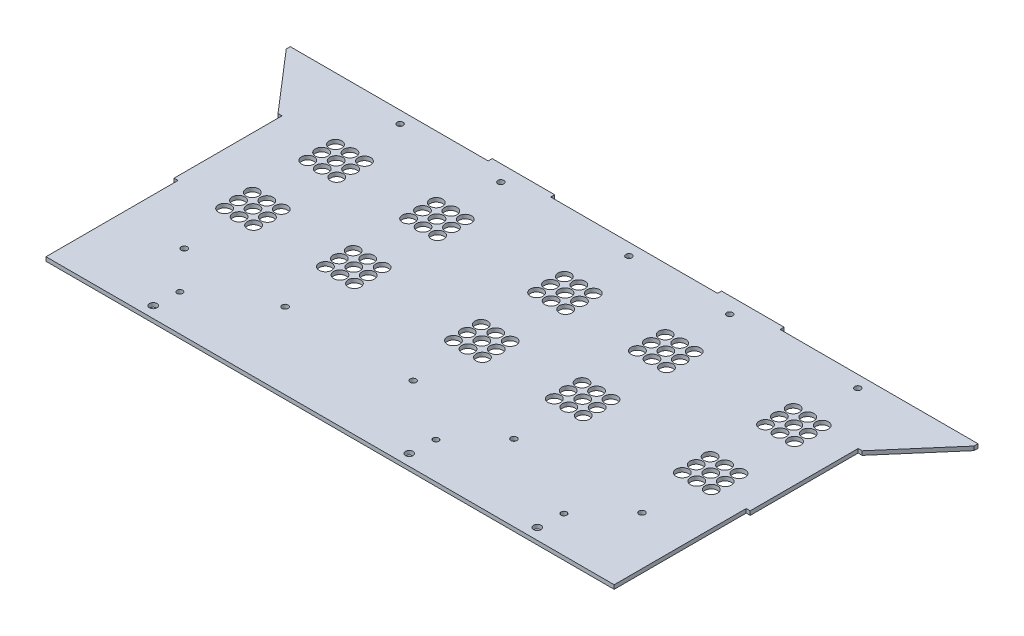
SolidWorks part; units mm, degrees
material "6061-T6 (SS)"
ref_plane "X-Y Datum" through (0, 0, 0) normal (0, 0, 1) x (1, 0, 0)
ref_plane "X-Z Datum" through (0, 0, 0) normal (0, 1, 0) x (1, 0, 0)
ref_plane "Y-Z Datum" through (0, 0, 0) normal (1, 0, 0) x (0, 0, -1)
sketch "Sketch1" plane through (0, 0, 0) normal (0, 0, 1) x (1, 0, 0)
  line L1 (-228.6114, -1.5875) -> (228.6114, -1.5875)
  line L2 (-228.6114, -1.5875) -> (-228.6114, 1.5875)
  line L3 (-228.6114, 1.5875) -> (228.6114, 1.5875)
  line L4 (228.6114, -1.5875) -> (228.6114, 1.5875)
  line L5 (-228.6114, -1.5875) -> (228.6114, 1.5875) construction
  line L6 (-228.6114, 1.5875) -> (228.6114, -1.5875) construction
  point P0 (0, 0)
  dimension "D1" = 3.175
  dimension "D2" = 457.2229
extrude "Boss-Extrude1" add sketch "Sketch1" along normal blind 241.2744
sketch "Sketch4" plane through (0, -1.5875, 0) normal (0, -1, 0) x (1, 0, 0)
  line L0 (-228.6114, 0) -> (-272.8862, 0)
  line L2 (-228.6114, 241.2744) -> (-228.6114, 0) construction
  line L3 (-228.6114, 50.8) -> (-228.6114, 0)
  line L4 (-272.8862, 0) -> (-272.8862, 3.175)
  line L6 (-228.6114, 50.8) -> (-231.7864, 50.8)
  line L7 (-231.7864, 50.8) -> (-272.8862, 3.175)
  line L31 (-228.6114, 0) -> (228.6114, 0)
  line L40 (-228.6114, 241.2744) -> (-228.6114, 0)
  line L41 (228.6114, 241.2744) -> (-228.6114, 241.2744)
  line L42 (228.6114, 0) -> (228.6114, 241.2744)
  line L51 (-228.6114, 0) -> (228.6114, 0)
  line L60 (-228.6114, 241.2744) -> (-228.6114, 0)
  line L61 (228.6114, 241.2744) -> (-228.6114, 241.2744)
  line L62 (228.6114, 0) -> (228.6114, 241.2744)
  point P2 (0, 0)
  point P11 (-271.03, 3.175)
  line M15 (-228.6114, 241.2744) -> (-228.6114, 0)
  dimension "D1" = 44.2747
  dimension "D2" = 50.8
  dimension "D3" = 3.175
  dimension "D4" = 3.175
  dimension "D5" = 0
extrude "Boss-Extrude3" add sketch "Sketch4" against normal blind 3.175 contours L6 L7 L4 L0 M15 region at (-244.2491, -1.5875, 18.0626)
mirror "Mirror1" about plane through (0, 0, 0) normal (1, 0, 0) of "Boss-Extrude3"
sketch "Sketch5" plane through (0, -1.5875, 0) normal (0, -1, 0) x (1, 0, 0)
  line L1 (-228.6114, 241.2744) -> (-225.4364, 241.2744)
  line L2 (-228.6114, 241.2744) -> (-228.6114, 136.4994)
  line L3 (-228.6114, 136.4994) -> (-225.4364, 136.4994)
  line L4 (-225.4364, 241.2744) -> (-225.4364, 136.4994)
  dimension "D1" = 3.175
  dimension "D2" = 104.775
extrude "Cut-Extrude2" cut sketch "Sketch5" against normal blind 3.175
mirror "Mirror2" about plane through (0, 0, 0) normal (1, 0, 0) of "Cut-Extrude2"
sketch "Sketch37" plane through (0, 1.5875, 0) normal (0, 1, 0) x (1, 0, 0)
  line L0 (-149.2364, -241.2744) -> (-149.2364, -232.3844) construction
  line L1 (225.4364, -241.2744) -> (-225.4364, -241.2744) construction
  line L2 (-225.4364, -136.4994) -> (-225.4364, -241.2744) construction
  circle A0 centre (-149.2364, -232.3844) radius 3
  dimension "D1" = 8.89
  dimension "D3" = 6
  dimension "D2" = 76.2
extrude "Cut-Extrude12" cut sketch "Sketch37" against normal blind 3.175
pattern_linear "LPattern31" count 4 spacing 101.6 along (1, 0, 0) skipping (1, 0) of "Cut-Extrude12"
sketch "Sketch51" plane through (0, 1.5875, 0) normal (0, 1, 0) x (1, 0, 0)
  point P0 (-176.2216, -180.775)
  point P1 (-176.2216, -9.525)
  point P3 (-96.2064, -9.525)
  point P5 (-96.2064, -180.775)
hole_wizard "M4 Clearance Hole1" positions "Sketch55" profile "Sketch53" hole size "M4" standard "ANSI Metric" end condition up to next
sketch "Sketch55" plane through (0, 1.5875, 0) normal (0, 1, 0) x (1, 0, 0)
  point P0 (-176.2216, -180.775)
  point P3 (-176.2216, -9.525)
sketch "Sketch53" plane through (-176.2216, 1.5875, 180.775) normal (1, 0, 0) x (0, 0, 1)
  line L0 (0, 0) -> (0, 3.175)
  line L1 (0, 3.175) -> (2.4, 3.175)
  line L2 (2.4, 3.175) -> (2.4, 0)
  line L5 (2.4, 0) -> (0, 0)
  line L11 (0, -6.35) -> (0, 107.95) construction
  dimension "Thru Hole Dia." = 4.8
  dimension "Thru Hole Depth" = 3.175
hole_wizard "M4 Clearance Hole2" positions "Sketch58" profile "Sketch57" hole size "M4" standard "ANSI Metric" end condition up to next
sketch "Sketch58" plane through (0, 1.5875, 0) normal (0, 1, 0) x (1, 0, 0)
  point P0 (-96.2064, -180.775)
  point P3 (-96.2064, -9.525)
sketch "Sketch57" plane through (-96.2064, 1.5875, 180.775) normal (1, 0, 0) x (0, 0, 1)
  line L0 (0, 0) -> (0, 3.175)
  line L1 (0, 3.175) -> (2.4, 3.175)
  line L2 (2.4, 3.175) -> (2.4, 0)
  line L5 (2.4, 0) -> (0, 0)
  line L11 (0, -6.35) -> (0, 107.95) construction
  dimension "Thru Hole Dia." = 4.8
  dimension "Thru Hole Depth" = 3.175
pattern_linear "LPattern32" count 3 spacing 181.614 along (1, 0, 0) of "M4 Clearance Hole1"
pattern_linear "LPattern33" count 2 spacing 181.614 along (1, 0, 0) of "M4 Clearance Hole2"
sketch "Sketch59" plane through (0, 1.5875, 0) normal (0, 1, 0) x (1, 0, 0)
  circle A0 centre (-187.7216, -115.2567) radius 5 construction
  circle A1 centre (-176.2216, -115.2567) radius 5 construction
  circle A2 centre (-164.7216, -115.2567) radius 5 construction
  circle A3 centre (-164.7216, -126.2567) radius 5 construction
  circle A4 centre (-176.2216, -126.2567) radius 5 construction
  circle A5 centre (-187.7216, -126.2567) radius 5 construction
  circle A6 centre (-187.7216, -137.2567) radius 5 construction
  circle A7 centre (-176.2216, -137.2567) radius 5 construction
  circle A8 centre (-164.7216, -137.2567) radius 5 construction
  circle A9 centre (-187.7216, -115.2567) radius 5
  circle A10 centre (-176.2216, -115.2567) radius 5
  circle A11 centre (-164.7216, -115.2567) radius 5
  circle A12 centre (-164.7216, -126.2567) radius 5
  circle A13 centre (-176.2216, -126.2567) radius 5
  circle A14 centre (-187.7216, -126.2567) radius 5
  circle A15 centre (-187.7216, -137.2567) radius 5
  circle A16 centre (-176.2216, -137.2567) radius 5
  circle A17 centre (-164.7216, -137.2567) radius 5
  circle A18 centre (-187.7216, -71.2567) radius 5 construction
  circle A19 centre (-176.2216, -71.2567) radius 5 construction
  circle A20 centre (-164.7216, -71.2567) radius 5 construction
  circle A21 centre (-176.2216, -60.2567) radius 5 construction
  circle A22 centre (-187.7216, -60.2567) radius 5 construction
  circle A23 centre (-187.7216, -49.2567) radius 5 construction
  circle A24 centre (-176.2216, -49.2567) radius 5 construction
  circle A25 centre (-164.7216, -49.2567) radius 5 construction
  circle A26 centre (-164.7216, -60.2567) radius 5 construction
  circle A27 centre (-187.7216, -71.2567) radius 5
  circle A28 centre (-176.2216, -71.2567) radius 5
  circle A29 centre (-164.7216, -71.2567) radius 5
  circle A30 centre (-176.2216, -60.2567) radius 5
  circle A31 centre (-187.7216, -60.2567) radius 5
  circle A32 centre (-187.7216, -49.2567) radius 5
  circle A33 centre (-176.2216, -49.2567) radius 5
  circle A34 centre (-164.7216, -49.2567) radius 5
  circle A35 centre (-164.7216, -60.2567) radius 5
  circle A36 centre (-107.7064, -126.2567) radius 5 construction
  circle A37 centre (-107.7064, -115.2567) radius 5 construction
  circle A38 centre (-107.7064, -137.2567) radius 5 construction
  circle A39 centre (-96.2064, -137.2567) radius 5 construction
  circle A40 centre (-96.2064, -126.2567) radius 5 construction
  circle A41 centre (-96.2064, -115.2567) radius 5 construction
  circle A42 centre (-84.7064, -115.2567) radius 5 construction
  circle A43 centre (-84.7064, -126.2567) radius 5 construction
  circle A44 centre (-84.7064, -137.2567) radius 5 construction
  circle A45 centre (-107.7064, -126.2567) radius 5
  circle A46 centre (-107.7064, -115.2567) radius 5
  circle A47 centre (-107.7064, -137.2567) radius 5
  circle A48 centre (-96.2064, -137.2567) radius 5
  circle A49 centre (-96.2064, -126.2567) radius 5
  circle A50 centre (-96.2064, -115.2567) radius 5
  circle A51 centre (-84.7064, -115.2567) radius 5
  circle A52 centre (-84.7064, -126.2567) radius 5
  circle A53 centre (-84.7064, -137.2567) radius 5
  circle A54 centre (-84.7064, -49.2567) radius 5 construction
  circle A55 centre (-96.2064, -49.2567) radius 5 construction
  circle A56 centre (-107.7064, -49.2567) radius 5 construction
  circle A57 centre (-107.7064, -60.2567) radius 5 construction
  circle A58 centre (-107.7064, -71.2567) radius 5 construction
  circle A59 centre (-96.2064, -71.2567) radius 5 construction
  circle A60 centre (-96.2064, -60.2567) radius 5 construction
  circle A61 centre (-84.7064, -60.2567) radius 5 construction
  circle A62 centre (-84.7064, -71.2567) radius 5 construction
  circle A63 centre (-84.7064, -49.2567) radius 5
  circle A64 centre (-96.2064, -49.2567) radius 5
  circle A65 centre (-107.7064, -49.2567) radius 5
  circle A66 centre (-107.7064, -60.2567) radius 5
  circle A67 centre (-107.7064, -71.2567) radius 5
  circle A68 centre (-96.2064, -71.2567) radius 5
  circle A69 centre (-96.2064, -60.2567) radius 5
  circle A70 centre (-84.7064, -60.2567) radius 5
  circle A71 centre (-84.7064, -71.2567) radius 5
extrude "Cut-Extrude13" cut sketch "Sketch59" against normal through all contours A34 | A33 | A32 | A31 | A35 | A29 | A28 | A27 | A15 | A16 | A17 | A12 | A13 | A14 | A11 | A10 | A9 | A30 region at (-187.7216, 1.5875, 115.2567) region at (-176.2216, 1.5875, 115.2567) region at (-164.7216, 1.5875, 115.2567) region at (-164.7216, 1.5875, 126.2567) region at (-176.2216, 1.5875, 126.2567) region at (-187.7216, 1.5875, 126.2567) region at (-187.7216, 1.5875, 137.2567) region at (-176.2216, 1.5875, 137.2567) region at (-164.7216, 1.5875, 137.2567) region at (-187.7216, 1.5875, 71.2567) region at (-176.2216, 1.5875, 71.2567) region at (-164.7216, 1.5875, 71.2567) region at (-187.7216, 1.5875, 60.2567) region at (-187.7216, 1.5875, 49.2567) region at (-176.2216, 1.5875, 49.2567) region at (-164.7216, 1.5875, 49.2567) region at (-164.7216, 1.5875, 60.2567)
pattern_linear "LPattern34" count 3 spacing 181.614 along (1, 0, 0) of "Cut-Extrude13"
sketch "Sketch60" plane through (0, 1.5875, 0) normal (0, 1, 0) x (1, 0, 0)
  circle A1 centre (-164.7216, -137.2567) radius 5
  circle A2 centre (-164.7216, -137.2567) radius 5
  circle A3 centre (-176.2216, -137.2567) radius 5
  circle A4 centre (-176.2216, -137.2567) radius 5
  circle A5 centre (-187.7216, -137.2567) radius 5
  circle A6 centre (-187.7216, -137.2567) radius 5
  circle A7 centre (-187.7216, -126.2567) radius 5
  circle A8 centre (-187.7216, -126.2567) radius 5
  circle A9 centre (-176.2216, -126.2567) radius 5
  circle A10 centre (-176.2216, -126.2567) radius 5
  circle A11 centre (-164.7216, -126.2567) radius 5
  circle A12 centre (-164.7216, -126.2567) radius 5
  circle A13 centre (-164.7216, -115.2567) radius 5
  circle A14 centre (-164.7216, -115.2567) radius 5
  circle A15 centre (-176.2216, -115.2567) radius 5
  circle A16 centre (-176.2216, -115.2567) radius 5
  circle A17 centre (-187.7216, -115.2567) radius 5
  circle A18 centre (-187.7216, -115.2567) radius 5
  circle A19 centre (-164.7216, -71.2567) radius 5
  circle A20 centre (-164.7216, -71.2567) radius 5
  circle A21 centre (-176.2216, -71.2567) radius 5
  circle A22 centre (-176.2216, -71.2567) radius 5
  circle A23 centre (-187.7216, -71.2567) radius 5
  circle A24 centre (-187.7216, -71.2567) radius 5
  circle A25 centre (-164.7216, -60.2567) radius 5
  circle A26 centre (-164.7216, -60.2567) radius 5
  circle A27 centre (-164.7216, -49.2567) radius 5
  circle A28 centre (-164.7216, -49.2567) radius 5
  circle A29 centre (-176.2216, -49.2567) radius 5
  circle A30 centre (-176.2216, -49.2567) radius 5
  circle A31 centre (-187.7216, -49.2567) radius 5
  circle A32 centre (-187.7216, -49.2567) radius 5
  circle A33 centre (-187.7216, -60.2567) radius 5
  circle A34 centre (-187.7216, -60.2567) radius 5
  circle A35 centre (-176.2216, -60.2567) radius 5
  circle A36 centre (-176.2216, -60.2567) radius 5
  circle A37 centre (-84.7064, -126.2567) radius 5
  circle A38 centre (-84.7064, -126.2567) radius 5
  circle A39 centre (-84.7064, -115.2567) radius 5
  circle A40 centre (-84.7064, -115.2567) radius 5
  circle A41 centre (-96.2064, -115.2567) radius 5
  circle A42 centre (-96.2064, -115.2567) radius 5
  circle A43 centre (-96.2064, -126.2567) radius 5
  circle A44 centre (-96.2064, -126.2567) radius 5
  circle A45 centre (-96.2064, -137.2567) radius 5
  circle A46 centre (-96.2064, -137.2567) radius 5
  circle A47 centre (-107.7064, -137.2567) radius 5
  circle A48 centre (-107.7064, -137.2567) radius 5
  circle A49 centre (-107.7064, -115.2567) radius 5
  circle A50 centre (-107.7064, -115.2567) radius 5
  circle A51 centre (-107.7064, -126.2567) radius 5
  circle A52 centre (-107.7064, -126.2567) radius 5
  circle A53 centre (-84.7064, -137.2567) radius 5
  circle A54 centre (-84.7064, -137.2567) radius 5
  circle A55 centre (-84.7064, -71.2567) radius 5
  circle A56 centre (-84.7064, -71.2567) radius 5
  circle A57 centre (-84.7064, -60.2567) radius 5
  circle A58 centre (-84.7064, -60.2567) radius 5
  circle A59 centre (-96.2064, -60.2567) radius 5
  circle A60 centre (-96.2064, -60.2567) radius 5
  circle A61 centre (-96.2064, -71.2567) radius 5
  circle A62 centre (-96.2064, -71.2567) radius 5
  circle A63 centre (-107.7064, -71.2567) radius 5
  circle A64 centre (-107.7064, -71.2567) radius 5
  circle A65 centre (-107.7064, -60.2567) radius 5
  circle A66 centre (-107.7064, -60.2567) radius 5
  circle A67 centre (-107.7064, -49.2567) radius 5
  circle A68 centre (-107.7064, -49.2567) radius 5
  circle A69 centre (-96.2064, -49.2567) radius 5
  circle A70 centre (-96.2064, -49.2567) radius 5
  circle A71 centre (-84.7064, -49.2567) radius 5
  circle A72 centre (-84.7064, -49.2567) radius 5
  dimension "D1" = 0
  dimension "D2" = 0
  dimension "D3" = 0
  dimension "D4" = 0
  dimension "D5" = 0
  dimension "D6" = 0
  dimension "D7" = 0
  dimension "D8" = 0
  dimension "D9" = 0
  dimension "D10" = 0
  dimension "D11" = 0
  dimension "D12" = 0
  dimension "D13" = 0
  dimension "D14" = 0
  dimension "D15" = 0
  dimension "D16" = 0
  dimension "D17" = 0
  dimension "D18" = 0
  dimension "D19" = 0
  dimension "D20" = 0
  dimension "D21" = 0
  dimension "D22" = 0
  dimension "D23" = 0
  dimension "D24" = 0
  dimension "D25" = 0
  dimension "D26" = 0
  dimension "D27" = 0
  dimension "D28" = 0
  dimension "D29" = 0
  dimension "D30" = 0
  dimension "D31" = 0
  dimension "D32" = 0
  dimension "D33" = 0
  dimension "D34" = 0
  dimension "D35" = 0
  dimension "D36" = 0
extrude "Cut-Extrude14" cut sketch "Sketch60" against normal through all contours A48 | A46 | A54 | A38 | A52 | A44 | A40 | A42 | A50 | A72 | A58 | A60 | A70 | A68 | A64 | A66 | A62 | A56
pattern_linear "LPattern35" count 2 spacing 181.614 along (1, 0, 0) of "Cut-Extrude14"
sketch "Sketch61" plane through (0, 1.5875, 0) normal (0, 1, 0) x (1, 0, 0)
  point P0 (-148.21, -212.285)
  point P1 (54.99, -212.285)
  point P3 (156.59, -212.285)
hole_wizard "M4 Clearance Hole3" positions "Sketch61" profile "Sketch62" hole size "M4" standard "ANSI Metric" end condition through all
sketch "Sketch62" plane through (-148.21, 1.5875, 212.285) normal (1, 0, 0) x (0, 0, 1)
  line L0 (0, 0) -> (0, 3.175)
  line L1 (0, 3.175) -> (2.25, 3.175)
  line L2 (2.25, 3.175) -> (2.25, 0)
  line L5 (2.25, 0) -> (0, 0)
  line L11 (0, -6.35) -> (0, 107.95) construction
  dimension "Thru Hole Dia." = 4.5
  dimension "Thru Hole Depth" = 3.175
sketch "Sketch63" plane through (0, 0, 0) normal (0, 0, -1) x (-1, 0, 0)
  line L0 (-66.1907, 1.5875) -> (-66.1907, -1.5875) construction
  line L1 (-115.8495, 1.5875) -> (-115.8495, -1.5875) construction
  line L2 (-115.8495, -1.5875) -> (-66.1907, -1.5875) construction
  line L3 (-66.1907, 1.5875) -> (-66.1907, -1.5875)
  line L4 (-115.8495, 1.5875) -> (-115.8495, -1.5875)
  line L5 (-115.8495, -1.5875) -> (-66.1907, -1.5875)
  line L6 (-228.1875, 1.7703) -> (228.1875, 1.7703) construction
  line L7 (-228.1875, 1.7703) -> (228.1875, 1.7703)
  line L8 (115.8495, 1.5875) -> (115.8495, -1.5875) construction
  line L9 (66.1907, 1.5875) -> (66.1907, -1.5875) construction
  line L10 (115.8495, -1.5875) -> (66.1907, -1.5875) construction
  line L11 (115.8495, 1.5875) -> (115.8495, -1.5875)
  line L12 (66.1907, 1.5875) -> (66.1907, -1.5875)
  line L13 (115.8495, -1.5875) -> (66.1907, -1.5875)
  line L14 (-272.8862, 1.5875) -> (272.8862, 1.5875) construction
  line L15 (-272.8862, 1.5875) -> (272.8862, 1.5875)
  line M1 (-272.8862, -1.5875) -> (272.8862, -1.5875)
  line M3 (272.8862, 1.5875) -> (-272.8862, 1.5875)
extrude "Boss-Extrude4" add sketch "Sketch63" along normal blind 3.175 contours L15 L12 L13 L11 | L4 L3 M3 M1 region at (91.0201, 0, 0) region at (-91.0201, 0, 0)
